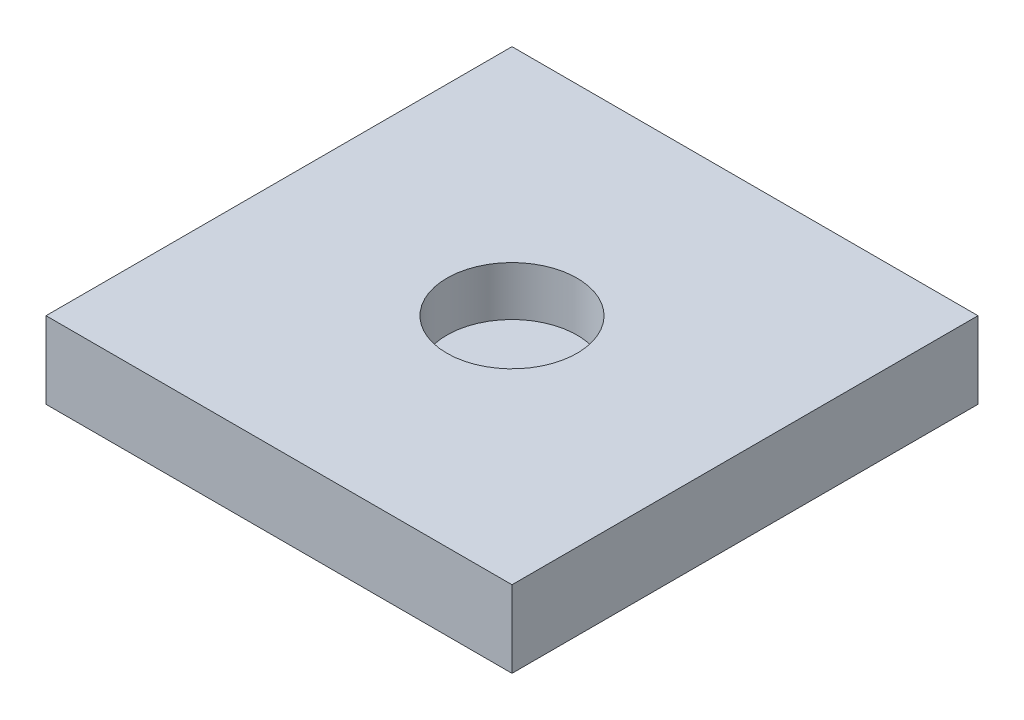
SolidWorks part; units mm, degrees
ref_plane "Front Plane" through (0, 0, 0) normal (0, 0, 1) x (1, 0, 0)
ref_plane "Top Plane" through (0, 0, 0) normal (0, 1, 0) x (1, 0, 0)
ref_plane "Right Plane" through (0, 0, 0) normal (1, 0, 0) x (0, 0, -1)
sketch "Sketch1" plane through (0, 0, 0) normal (0, 1, 0) x (1, 0, 0)
  line L1 (170, 170) -> (-170, 170)
  line L2 (170, 170) -> (170, -170)
  line L3 (170, -170) -> (-170, -170)
  line L4 (-170, 170) -> (-170, -170)
  line L5 (170, 170) -> (-170, -170) construction
  line L6 (170, -170) -> (-170, 170) construction
  point P0 (0, 0)
  dimension "D1" = 340
  dimension "D2" = 340
extrude "Boss-Extrude1" add sketch "Sketch1" along normal blind 56
sketch "Sketch2" plane through (0, 56, 0) normal (0, 1, 0) x (1, 0, 0)
  circle A0 centre (0, 0) radius 47.5
  dimension "D1" = 95
extrude "Cut-Extrude1" cut sketch "Sketch2" against normal blind 36 contours A0
